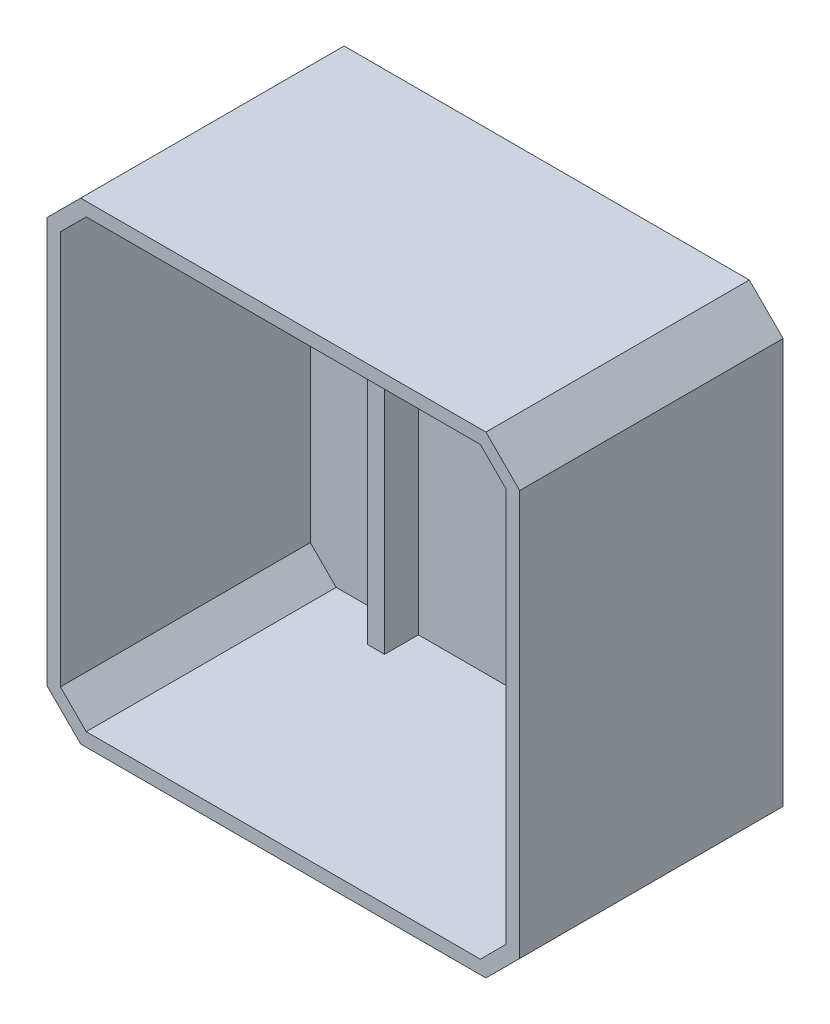
SolidWorks part; units mm, degrees
ref_plane "Front Plane" through (0, 0, 0) normal (0, 0, 1) x (1, 0, 0)
ref_plane "Top Plane" through (0, 0, 0) normal (0, 1, 0) x (1, 0, 0)
ref_plane "Right Plane" through (0, 0, 0) normal (1, 0, 0) x (0, 0, -1)
sketch "Sketch1" plane through (0, 0, 0) normal (0, 0, 1) x (1, 0, 0)
  line L1 (51.8222, 34.9266) -> (121.8222, 34.9266)
  line L2 (51.8222, 34.9266) -> (51.8222, -35.0734)
  line L3 (51.8222, -35.0734) -> (121.8222, -35.0734)
  line L4 (121.8222, 34.9266) -> (121.8222, -35.0734)
  dimension "D1" = 70
  dimension "D2" = 70
ref_plane "Plane1" through (0, 0, -39) normal (0, 0, 1) x (1, 0, 0)
extrude "Boss-Extrude1" add sketch "Sketch1" against normal blind 39
chamfer "Chamfer1" distance 5 angle 45 4 edges at (121.8222, -35.0734, -19.5) (51.8222, -35.0734, -19.5) (51.8222, 34.9266, -19.5) (121.8222, 34.9266, -19.5)
shell "Shell1" thickness 2 removed face at (86.8222, -0.0734, 0)
sketch "Sketch3" plane through (0, 0, -37) normal (0, 0, 1) x (1, 0, 0)
  line L0 (115.9938, 32.9266) -> (57.6506, 32.9266) construction
  line L1 (67.3222, 32.9266) -> (69.8222, 32.9266)
  line L2 (67.3222, 32.9266) -> (67.3222, -33.0734)
  line L3 (67.3222, -33.0734) -> (69.8222, -33.0734)
  line L4 (69.8222, 32.9266) -> (69.8222, -33.0734)
  line L5 (57.6506, -33.0734) -> (115.9938, -33.0734) construction
  line L6 (53.8222, 29.0982) -> (53.8222, -29.2449) construction
  line L8 (86.8222, 32.9266) -> (86.8222, -50.5449) construction
  line L9 (106.3222, -33.0734) -> (103.8222, -33.0734)
  line L10 (103.8222, 32.9266) -> (103.8222, -33.0734)
  line L11 (106.3222, 32.9266) -> (103.8222, 32.9266)
  line L12 (106.3222, 32.9266) -> (106.3222, -33.0734)
  dimension "D1" = 2.5
  dimension "D2" = 13.5
extrude "Boss-Extrude2" add sketch "Sketch3" along normal blind 5
